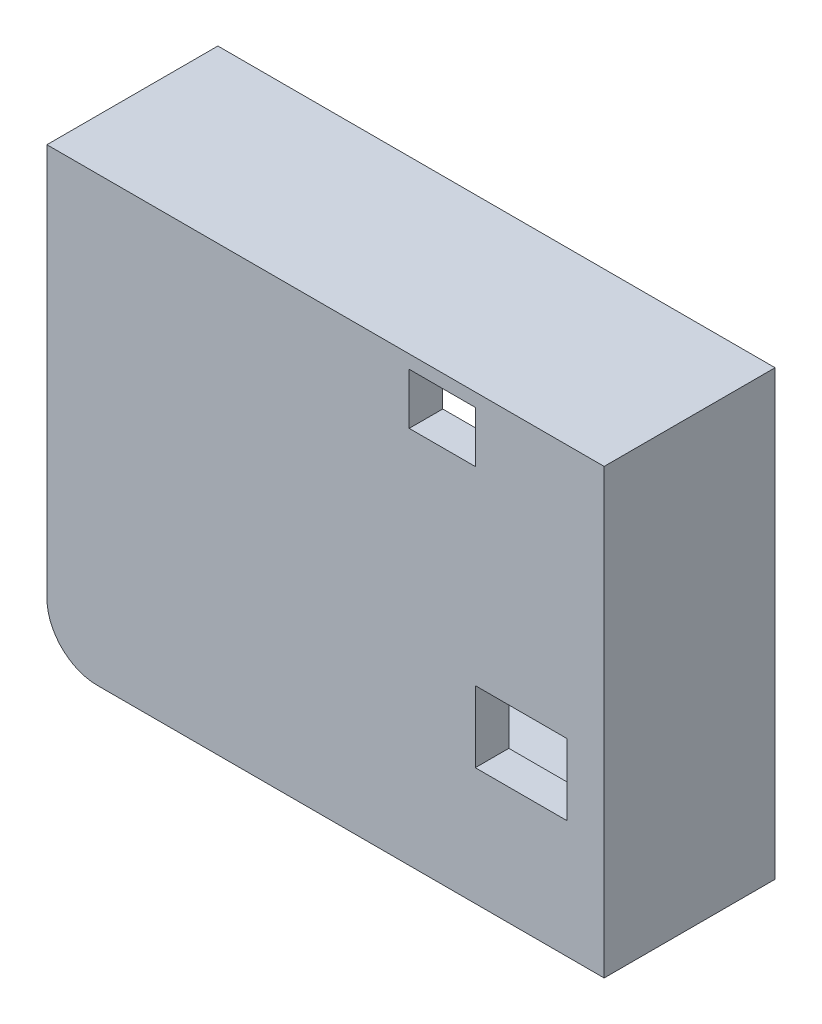
SolidWorks part; units mm, degrees
note: The reader was unsure of these and kept them because the rebuilt part matched: shared geometry of "Sketch2<8>".
ref_plane "Front Plane" through (0, 0, 0) normal (0, 0, 1) x (1, 0, 0)
ref_plane "Top Plane" through (0, 0, 0) normal (0, 1, 0) x (1, 0, 0)
ref_plane "Right Plane" through (0, 0, 0) normal (1, 0, 0) x (0, 0, -1)
sketch "Sketch2" plane through (0, 0, 0) normal (0, 0, 1) x (1, 0, 0)
  line L1 (131.0919, -125.165) -> (164.3077, -125.165)
  line L2 (131.0919, -125.165) -> (131.0919, -98.7543)
  line L3 (131.0919, -98.7543) -> (164.3077, -98.7543)
  line L4 (164.3077, -125.165) -> (164.3077, -98.7543)
  line L5 (131.0919, -125.165) -> (164.3077, -98.7543) construction
  line L6 (131.0919, -98.7543) -> (164.3077, -125.165) construction
  line L8 (137, -99.55) -> (162.1, -99.55) construction
  line L9 (131.0919, -113.8605) -> (128.175, -113.8605)
  line L10 (131.0919, -113.8605) -> (131.0919, -106.0949)
  line L11 (131.0919, -106.0949) -> (128.175, -106.0949)
  line L12 (128.175, -113.8605) -> (128.175, -106.0949)
  line L13 (131.0919, -113.8605) -> (128.175, -106.0949) construction
  line L14 (131.0919, -106.0949) -> (128.175, -113.8605) construction
  line L15 (164.3077, -114.8619) -> (164.8283, -114.8619)
  line L16 (164.3077, -114.8619) -> (164.3077, -107.0963)
  line L17 (164.3077, -107.0963) -> (164.8283, -107.0963)
  line L18 (164.8283, -114.8619) -> (164.8283, -107.0963)
  line L19 (164.3077, -114.8619) -> (164.8283, -107.0963) construction
  line L20 (164.3077, -107.0963) -> (164.8283, -114.8619) construction
  line L21 (152.6871, -102.6012) -> (156.6267, -102.6012)
  line L22 (152.6871, -102.6012) -> (152.6871, -99.55)
  line L23 (152.6871, -99.55) -> (156.6267, -99.55)
  line L24 (156.6267, -102.6012) -> (156.6267, -99.55)
  line L25 (152.6871, -102.6012) -> (156.6267, -99.55) construction
  line L26 (152.6871, -99.55) -> (156.6267, -102.6012) construction
  line L27 (162.1, -99.55) -> (162.1, -118.15) construction
  line L28 (162.1, -118.15) -> (156.6267, -118.15)
  line L29 (162.1, -118.15) -> (162.1, -113.911)
  line L30 (162.1, -113.911) -> (156.6267, -113.911)
  line L31 (156.6267, -118.15) -> (156.6267, -113.911)
  line L32 (162.1, -118.15) -> (156.6267, -113.911) construction
  line L33 (162.1, -113.911) -> (156.6267, -118.15) construction
  line L34 (134.0919, -125.165) -> (191.3476, -125.165) construction
  line L35 (162.3077, -99.55) -> (133.0919, -99.55)
  line L36 (162.3077, -99.55) -> (162.3077, -123.165)
  line L37 (162.3077, -123.165) -> (133.0919, -123.165)
  line L38 (133.0919, -99.55) -> (133.0919, -123.165)
  line L39 (162.3077, -99.55) -> (133.0919, -123.165) construction
  line L40 (162.3077, -123.165) -> (133.0919, -99.55) construction
  line L41 (131.0919, -122.165) -> (131.0919, -96.293) construction
  point P4 (147.6998, -111.9596)
  point P13 (129.6334, -109.9777)
  point P14 (164.568, -110.9791)
  point P19 (154.6569, -101.0756)
  point P26 (159.3634, -116.0305)
  point P33 (147.6998, -111.3575)
  dimension "D1" = 2
  dimension "D2" = 2
  dimension "D3" = 0
  dimension "D4" = 0
  dimension "D6" = 2
  dimension "D7" = 0
extrude "Perimeter" add sketch "Sketch2" along normal up to surface (8.19 mm away) from offset 2 contours L1 L4 L3 L2 L38 L35 L23 L36 L37
fillet "Fillet1" radius 3 2 edges at (133.0919, -123.165, -2.095) (131.0919, -125.165, -2.095)
extrude "Boss-Extrude3" add sketch "Sketch2<8>" along normal blind 2 from offset 2 contours L35 L38 L37 L36 L24 L21 L22 L28 L31 L30 L29 | L1 L4 L3 L2 L38 L35 L23 L36 L37
sketch "Sketch2<8>" plane through (0, 0, 0) normal (0, 0, 1) x (1, 0, 0) same geometry as "Sketch2"
fillet "Fillet3" radius 3 1 edges at (131.0919, -125.165, 3)
